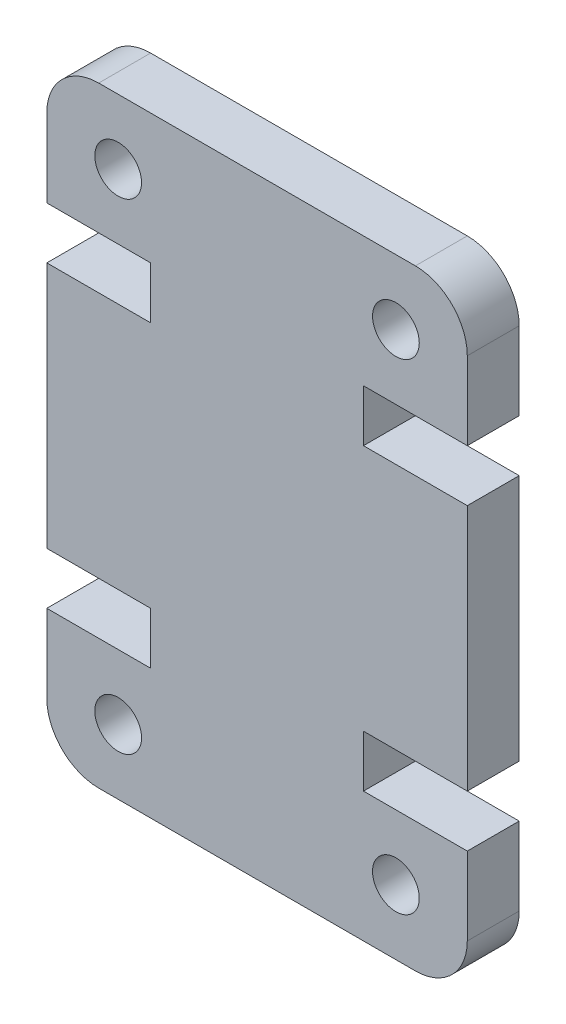
SolidWorks part; units mm, degrees
ref_plane "Front Plane" through (0, 0, 0) normal (0, 0, 1) x (1, 0, 0)
ref_plane "Top Plane" through (0, 0, 0) normal (0, 1, 0) x (1, 0, 0)
ref_plane "Right Plane" through (0, 0, 0) normal (1, 0, 0) x (0, 0, -1)
sketch "Sketch1" plane through (0, 0, 0) normal (0, 0, 1) x (1, 0, 0)
  line L0 (8.1, 23.525) -> (8.1, 0) construction
  line L1 (0, 11.7625) -> (16.2, 11.7625) construction
  line L2 (16.2, 5) -> (16.2, 2)
  line L3 (12.2, 5) -> (16.2, 5)
  line L4 (16.2, 7) -> (12.2, 7)
  line L5 (12.2, 7) -> (12.2, 5)
  line L6 (16.2, 7) -> (16.2, 16.525)
  line L7 (0, 18.525) -> (0, 21.525)
  line L8 (4, 18.525) -> (0, 18.525)
  line L9 (0, 16.525) -> (4, 16.525)
  line L10 (4, 16.525) -> (4, 18.525)
  line L11 (2, 23.525) -> (14.2, 23.525)
  line L12 (12.2, 16.525) -> (12.2, 18.525)
  line L13 (16.2, 16.525) -> (12.2, 16.525)
  line L14 (12.2, 18.525) -> (16.2, 18.525)
  line L15 (16.2, 18.525) -> (16.2, 21.525)
  line L20 (0, 7) -> (0, 16.525)
  line L23 (2, 0) -> (14.2, 0)
  line L30 (4, 7) -> (4, 5)
  line L32 (0, 7) -> (4, 7)
  line L33 (4, 5) -> (0, 5)
  line L39 (0, 5) -> (0, 2)
  circle A0 centre (13.45, 2.5) radius 0.9
  arc A2 (16.2, 2) -> (14.2, 0) centre (14.2, 2) cw
  circle A4 centre (2.75, 21.025) radius 0.9
  arc A5 (0, 21.525) -> (2, 23.525) centre (2, 21.525) cw
  arc A7 (16.2, 21.525) -> (14.2, 23.525) centre (14.2, 21.525) ccw
  circle A9 centre (13.45, 21.025) radius 0.9
  arc A11 (0, 2) -> (2, 0) centre (2, 2) ccw
  circle A13 centre (2.75, 2.5) radius 0.9
  point P18 (8.1, 11.7625)
  dimension "D2" = 2
  dimension "D4" = 1.8
  dimension "D3" = 2.75
  dimension "D5" = 8.1
  dimension "D6" = 2.5
  dimension "D10" = 11.7625
  dimension "D7" = 5
extrude "Boss-Extrude1" add sketch "Sketch1" along normal blind 2
equation "\"D10@Sketch1\"= ( \"HL@parametersSketch@prostheticParameters.SLDPRT\" * 0.165 - 3 - 4 ) / 2 'MIP length - Sil. Sht MIP - Sil. Sht DIP"
equation "\"D5@Sketch1\"= \"fingerWidth@parametersSketch@prostheticParameters.SLDPRT\" / 2'MIP width"
equation "\"D4@Sketch1\"= 1.5 + \"tol1@parametersSketch@prostheticParameters.SLDPRT\""
